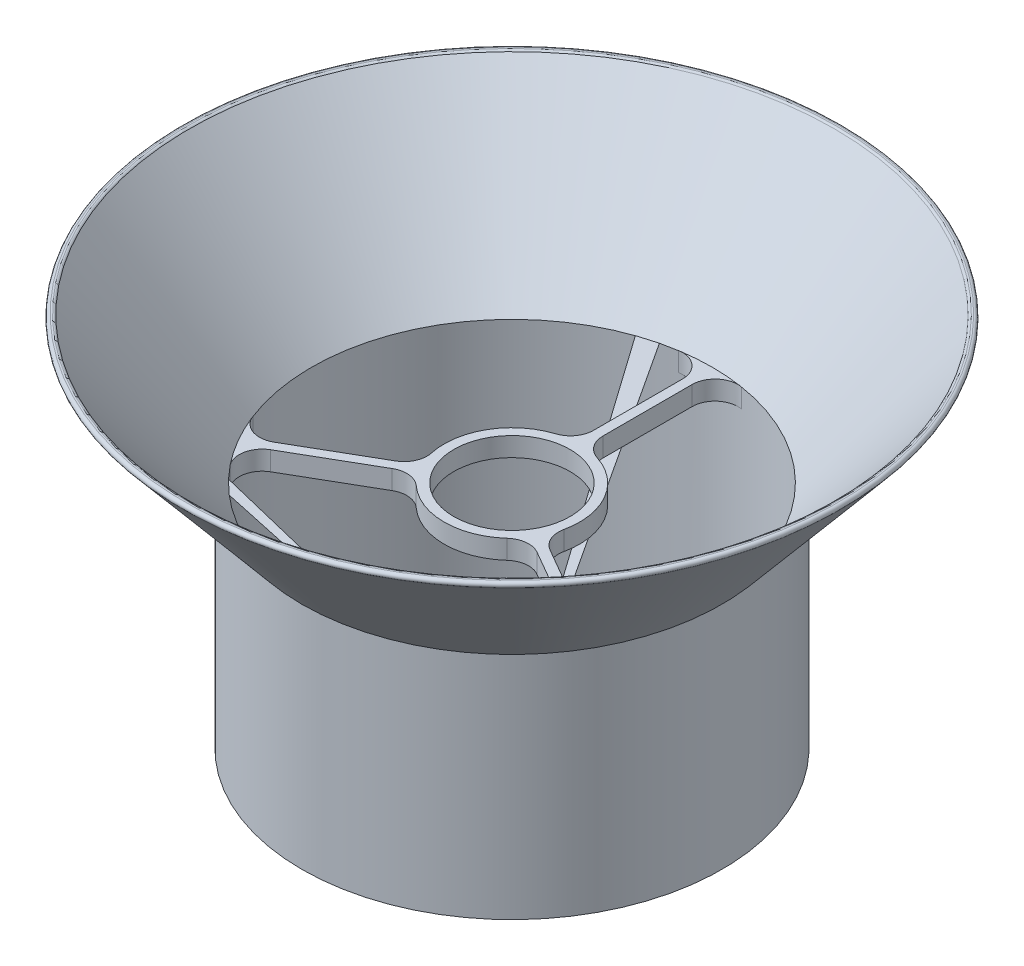
SolidWorks part; units mm, degrees
ref_plane "Front Plane" through (0, 0, 0) normal (0, 0, 1) x (1, 0, 0)
ref_plane "Top Plane" through (0, 0, 0) normal (0, 1, 0) x (1, 0, 0)
ref_plane "Right Plane" through (0, 0, 0) normal (1, 0, 0) x (0, 0, -1)
sketch "Sketch1" plane through (0, 0, 0) normal (0, 1, 0) x (1, 0, 0)
  circle A0 centre (0, 0) radius 66.548
  circle A1 centre (0, 0) radius 69.723
  dimension "D1" = 133.096
  dimension "D2" = 3.175
extrude "Boss-Extrude1" add sketch "Sketch1" along normal blind 76.2
sketch "Sketch2" plane through (0, 76.2, 0) normal (0, 1, 0) x (1, 0, 0)
  circle A0 centre (0, 0) radius 19.304
  circle A1 centre (0, 0) radius 22.479
  dimension "D1" = 38.608
  dimension "D2" = 3.175
extrude "Boss-Extrude2" add sketch "Sketch2" against normal blind 6.35 separate body
sketch "Sketch3" plane through (0, 76.2, 0) normal (0, 1, 0) x (1, 0, 0)
  line L0 (-1.5875, 22.4229) -> (-1.5875, 66.5291)
  line L1 (1.5875, 22.4229) -> (1.5875, 66.5291)
  line L2 (-1.5875, 51.781) -> (1.5875, 51.781) construction
  circle A0 centre (0, 0) radius 22.479 construction
  circle A1 centre (0, 0) radius 66.548 construction
  arc A2 (1.5875, 66.5291) -> (-1.5875, 66.5291) centre (0, 0) ccw
  arc A3 (1.5875, 22.4229) -> (-1.5875, 22.4229) centre (0, 0) ccw
  point P10 (0, 51.781)
  dimension "D1" = 3.175
extrude "Boss-Extrude3" add sketch "Sketch3" against normal up to surface (6.35 mm away) up to face at (0, 69.85, 19.304)
pattern_circular "CirPattern1" count 3 over 360 about axis through (0, 69.85, 0) along (0, 1, 0) of "Boss-Extrude3"
ref_axis "Axis1" through (0, 76.2, 0) along (0, -1, 0)
sketch "Sketch5" plane through (0, 0, 0) normal (0, 0, 1) x (1, 0, 0)
  line L0 (66.5291, 76.2) -> (107.3461, 124.8438)
  line L1 (69.723, 76.2) -> (110.54, 124.8438)
  line L2 (69.723, 0) -> (69.723, 76.2) construction
  line L3 (107.3461, 124.8438) -> (110.54, 124.8438)
  line L4 (66.5291, 76.2) -> (69.723, 76.2)
  dimension "D1" = 140
  dimension "D2" = 63.5
revolve "Revolve2" add sketch "Sketch5" angle 360 about axis through (0, 76.2, 0) along (0, -1, 0)
fillet "Fillet4" radius 7.62 12 edges at (-20.2125, 73.025, 9.8366) (-58.4096, 73.025, 31.8897) (-1.5875, 73.025, -22.4229) (-1.5875, 73.025, -66.5291) (1.5875, 73.025, -22.4229) (1.5875, 73.025, -66.5291) (58.4096, 73.025, 31.8897) (20.2125, 73.025, 9.8366) (56.8221, 73.025, 34.6393) (18.625, 73.025, 12.5863) (-18.625, 73.025, 12.5863) (-56.8221, 73.025, 34.6393)
fillet "Fillet6" radius 1.016 2 edges at (0, 124.8438, 110.54) (0, 124.8438, 107.3461)
